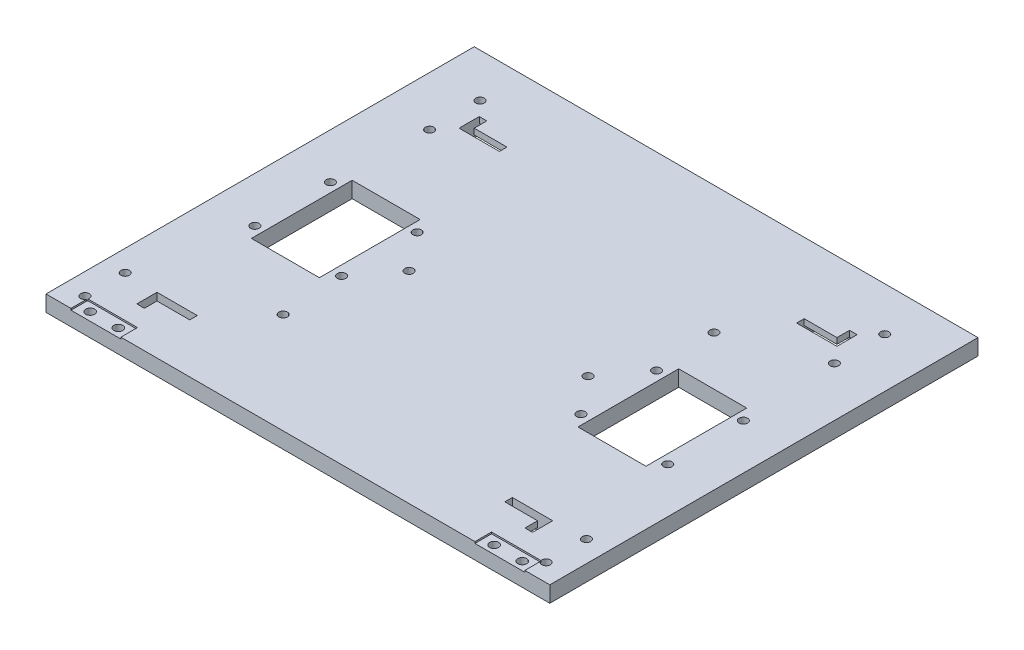
SolidWorks part; units mm, degrees
material "1023 Carbon Steel Sheet (SS)"
ref_plane "Front Plane" through (0, 0, 0) normal (0, 0, 1) x (1, 0, 0)
ref_plane "Top Plane" through (0, 0, 0) normal (0, 1, 0) x (1, 0, 0)
ref_plane "Right Plane" through (0, 0, 0) normal (1, 0, 0) x (0, 0, -1)
sketch "Sketch1" plane through (0, 0, 0) normal (0, 1, 0) x (1, 0, 0)
  line L1 (-100, -85) -> (100, -85)
  line L2 (-100, -85) -> (-100, 85)
  line L3 (-100, 85) -> (100, 85)
  line L4 (100, -85) -> (100, 85)
  line L5 (-100, -85) -> (100, 85) construction
  line L6 (-100, 85) -> (100, -85) construction
  point P0 (0, 0)
  dimension "D1" = 200
  dimension "D2" = 170
extrude "1/4\" Steel Plate" add sketch "Sketch1" along normal blind 6.35
ref_plane "Midplane" through (0, 0, 0) normal (-1, 0, 0) x (0, 0, 1)
sketch "Sketch2" plane through (0, 6.35, 0) normal (0, 1, 0) x (1, 0, 0)
  line L0 (-100, -85) -> (100, -85) construction
  line L1 (-90.094, -85) -> (-70.282, -85)
  line L2 (-90.094, -85) -> (-90.094, -78.396)
  line L3 (-90.094, -78.396) -> (-70.282, -78.396)
  line L4 (-70.282, -85) -> (-70.282, -78.396)
  line L5 (-100, 85) -> (-100, -85) construction
  dimension "D1" = 9.906
  dimension "D2" = 6.604
  dimension "D3" = 19.812
extrude "BladeHingeCut" cut sketch "Sketch2" against normal blind 0.635
hole_wizard "BladeHingeHole" positions "3DSketch2" profile "Sketch4" hole size "#8" standard "ANSI Inch" end condition through all
sketch3d "3DSketch2"
  line L0 (-90.094, 5.715, 85) -> (-70.282, 5.715, 85) construction
  line L10 (-80.188, 5.715, 78.396) -> (-80.188, 5.715, 85) construction
  line L11 (-70.282, 5.715, 78.396) -> (-90.094, 5.715, 78.396) construction
  point P0 (-74.6, 5.715, 81.698)
  point P2 (-85.776, 5.715, 81.698)
  dimension "D1" = 3.302
  dimension "D2" = 3.302
  dimension "D3" = 11.176
  dimension "D4" = 5.588
sketch "Sketch4" plane through (-74.6, 5.715, 81.698) normal (1, 0, 0) x (0, 0, 1)
  line L0 (0, 0) -> (0, 5.715)
  line L1 (0, 5.715) -> (1.778, 5.715)
  line L2 (1.778, 5.715) -> (1.778, 0)
  line L5 (1.778, 0) -> (0, 0)
  line L11 (0, -6.35) -> (0, 107.95) construction
  dimension "Thru Hole Dia." = 3.556
  dimension "Thru Hole Depth" = 5.715
sketch "Sketch5" plane through (0, 0, 0) normal (0, -1, 0) x (1, 0, 0)
  line L1 (-88.301, 79.173) -> (-83.251, 79.173)
  line L2 (-88.301, 79.173) -> (-88.301, 84.223)
  line L3 (-88.301, 84.223) -> (-83.251, 84.223)
  line L4 (-83.251, 79.173) -> (-83.251, 84.223)
  line L5 (-88.301, 79.173) -> (-83.251, 84.223) construction
  line L6 (-88.301, 84.223) -> (-83.251, 79.173) construction
  line L7 (-72.075, 79.173) -> (-77.125, 79.173)
  line L8 (-72.075, 79.173) -> (-72.075, 84.223)
  line L9 (-72.075, 84.223) -> (-77.125, 84.223)
  line L10 (-77.125, 79.173) -> (-77.125, 84.223)
  line L11 (-72.075, 79.173) -> (-77.125, 84.223) construction
  line L12 (-72.075, 84.223) -> (-77.125, 79.173) construction
  point P0 (-85.776, 81.698)
  point P6 (-74.6, 81.698)
  dimension "D1" = 5.05
  dimension "D2" = 5.05
  dimension "D3" = 5.05
  dimension "D4" = 5.05
extrude "BladeNutCut" cut sketch "Sketch5" against normal blind 2
mirror "BladeHingeMirror" about plane through (0, 0, 0) normal (-1, 0, 0) of "BladeNutCut", "BladeHingeHole", "BladeHingeCut"
sketch "Sketch6" plane through (0, 0, 0) normal (0, -1, 0) x (-1, 0, 0)
  line L0 (77.3259, -27.0397) -> (77.3259, 16.7603) construction
  line L1 (78.3259, 14.8603) -> (51.3259, 14.8603)
  line L2 (78.3259, 14.8603) -> (78.3259, -25.1397)
  line L3 (78.3259, -25.1397) -> (51.3259, -25.1397)
  line L4 (51.3259, 14.8603) -> (51.3259, -25.1397)
  line L5 (57.3259, 16.7603) -> (57.3259, -27.0397) construction
  point P6 (78.3259, -5.1397)
  dimension "D1" = 1
  dimension "D2" = 20
  dimension "D3" = 6
  dimension "D4" = 20
extrude "Cut-Extrude1" cut sketch "Sketch6" against normal up to surface (6.35 mm away) up to face at (0, 6.35, 54.4653)
sketch "Sketch7" plane through (0, 0, 0) normal (0, -1, 0) x (-1, 0, 0)
  line L0 (51.3259, -25.1397) -> (78.3259, -25.1397) construction
  line L1 (79.3259, -30.1397) -> (49.3259, -30.1397)
  line L2 (79.3259, -30.1397) -> (79.3259, -40.1397)
  line L3 (79.3259, -40.1397) -> (49.3259, -40.1397)
  line L4 (49.3259, -30.1397) -> (49.3259, -40.1397)
  line L5 (80.3259, 19.8603) -> (50.3259, 19.8603)
  line L6 (80.3259, 19.8603) -> (80.3259, 29.8603)
  line L7 (80.3259, 29.8603) -> (50.3259, 29.8603)
  line L8 (50.3259, 19.8603) -> (50.3259, 29.8603)
  line L9 (29.3259, -25.1397) -> (19.3259, -25.1397)
  line L10 (29.3259, -25.1397) -> (29.3259, 14.8603)
  line L11 (29.3259, 14.8603) -> (19.3259, 14.8603)
  line L12 (19.3259, -25.1397) -> (19.3259, 14.8603)
  line L17 (78.3259, -25.1397) -> (78.3259, 14.8603) construction
  line L18 (78.3259, 14.8603) -> (51.3259, 14.8603) construction
  line L19 (51.3259, 14.8603) -> (51.3259, -25.1397) construction
  line L29 (46.3259, -80.1397) -> (36.3259, -80.1397)
  line L30 (46.3259, -80.1397) -> (46.3259, -50.1397)
  line L31 (46.3259, -50.1397) -> (36.3259, -50.1397)
  line L32 (36.3259, -80.1397) -> (36.3259, -50.1397)
  line L33 (20, -70.1397) -> (-20, -70.1397)
  line L34 (20, -70.1397) -> (20, -60.1397)
  line L35 (20, -60.1397) -> (-20, -60.1397)
  line L36 (-20, -70.1397) -> (-20, -60.1397)
  line L37 (-100, 85) -> (100, 85) construction
  line L38 (36.3259, 39.8603) -> (46.3259, 39.8603)
  line L39 (36.3259, 39.8603) -> (36.3259, 69.8603)
  line L40 (36.3259, 69.8603) -> (46.3259, 69.8603)
  line L41 (46.3259, 39.8603) -> (46.3259, 69.8603)
  line L42 (20, 49.8603) -> (-20, 49.8603)
  line L43 (20, 49.8603) -> (20, 59.8603)
  line L44 (20, 59.8603) -> (-20, 59.8603)
  line L45 (-20, 49.8603) -> (-20, 59.8603)
  point P18 (0, 49.8603)
  point P55 (20, 54.8603)
  point P56 (36.3259, 54.8603)
  point P57 (20, -65.1397)
  point P58 (36.3259, -65.1397)
  point P60 (0, 85)
  dimension "D1" = 5
  dimension "D2" = 30
  dimension "D3" = 10
  dimension "D4" = 1
  dimension "D5" = 5
  dimension "D6" = 1
  dimension "D7" = 10
  dimension "D8" = 30
  dimension "D9" = 40
  dimension "D10" = 10
  dimension "D11" = 22
  dimension "D14" = 10
  dimension "D17" = 5
  dimension "D18" = 40
  dimension "D19" = 10
  dimension "D20" = 30
  dimension "D21" = 25
  dimension "D22" = 10
  dimension "D23" = 30
  dimension "D24" = 25
  dimension "D25" = 10
  dimension "D26" = 40
other "AlignGroup1"
extrude "Cut-Extrude2" cut sketch "Sketch7" against normal blind 5 contours L30 L29 L32 L31 | L34 L33 L36 L35 | L10 L9 L12 L11 | L2 L1 L4 L3 | L6 L5 L8 L7 | L39 L38 L41 L40 | L43 L42 L45 L44
sketch "Sketch8" plane through (0, 6.35, 0) normal (0, 1, 0) x (1, 0, 0)
  line L0 (-83.5459, -55) -> (-83.5459, -85) construction
  line L1 (-78.5459, -62.396) -> (-62.5459, -62.396)
  line L2 (-78.5459, -62.396) -> (-78.5459, -73.396)
  line L3 (-78.5459, -73.396) -> (-62.5459, -73.396)
  line L4 (-62.5459, -62.396) -> (-62.5459, -73.396)
  line L5 (-70.282, -78.396) -> (-90.094, -78.396) construction
  dimension "D1" = 11
  dimension "D2" = 16
  dimension "D3" = 5
  dimension "D4" = 5
extrude "Cut-Extrude3" cut sketch "Sketch8" along normal blind 4 from surface starting at face at (0, 0, -54.8603)
sketch "Sketch9" plane through (0, 4, 0) normal (0, -1, 0) x (1, 0, 0)
  line L0 (-78.5459, 62.396) -> (-62.5459, 62.396)
  line L9 (-78.5459, 62.396) -> (-78.5459, 70.396)
  line L10 (-78.5459, 73.396) -> (-78.5459, 62.396) construction
  line L11 (-78.5459, 70.396) -> (-75.5459, 70.396)
  line L12 (-75.5459, 70.396) -> (-75.5459, 65.396)
  line L13 (-75.5459, 65.396) -> (-62.5459, 65.396)
  line L14 (-62.5459, 62.396) -> (-62.5459, 73.396) construction
  line L15 (-62.5459, 65.396) -> (-62.5459, 62.396)
  dimension "D1" = 8
  dimension "D2" = 3
  dimension "D3" = 3
extrude "Cut-Extrude4" cut sketch "Sketch9" against normal up to surface (2.35 mm away) contours L13 L15 L0 L9 L11 L12 up to face at (-64.8259, 6.35, 5.1397)
sketch "Sketch10" plane through (0, 0, 0) normal (0, -1, 0) x (-1, 0, 0)
  line L1 (75, 65) -> (59, 65)
  line L2 (75, 65) -> (75, 54)
  line L3 (75, 54) -> (59, 54)
  line L4 (59, 65) -> (59, 54)
  line L6 (100, 85) -> (100, -85) construction
  line L7 (-100, 85) -> (100, 85) construction
  dimension "D1" = 11
  dimension "D2" = 16
  dimension "D3" = 25
  dimension "D4" = 20
extrude "Cut-Extrude5" cut sketch "Sketch10" against normal blind 4
sketch "Sketch11" plane through (0, 4, 0) normal (0, -1, 0) x (1, 0, 0)
  line L0 (-59, -54) -> (-75, -54)
  line L1 (-75, -54) -> (-75, -62)
  line L2 (-75, -54) -> (-75, -65) construction
  line L3 (-75, -62) -> (-72, -62)
  line L4 (-72, -62) -> (-72, -57)
  line L5 (-72, -57) -> (-59, -57)
  line L6 (-59, -65) -> (-59, -54) construction
  line L7 (-59, -57) -> (-59, -54)
  dimension "D1" = 3
  dimension "D2" = 3
  dimension "D3" = 8
extrude "Cut-Extrude6" cut sketch "Sketch11" against normal up to next
mirror "Mirror2" about plane through (0, 0, 0) normal (-1, 0, 0) of "Cut-Extrude6", "Cut-Extrude5", "Cut-Extrude4", "Cut-Extrude3", "Cut-Extrude2", "Cut-Extrude1"
hole_wizard "CSK for M3 Flat Head Machine Screw1" positions "Sketch12" profile "Sketch13" countersink size "M3" standard "ANSI Metric"
sketch "Sketch12" plane through (0, 0, 0) normal (0, -1, 0) x (-1, 0, 0)
  point P0 (-91.5503, -78)
  point P2 (-91.5503, -62)
  point P4 (-80.3371, 47.6378)
  point P7 (-80.3371, 67.6378)
  point P10 (-35.8509, -5.663)
  point P13 (-45.8509, 34.337)
  point P16 (35.8509, -5)
  point P19 (45.8509, -45)
  point P22 (91.5459, -62)
  point P25 (91.5459, -78)
  point P28 (80.3371, 47.6378)
  point P31 (80.3371, 67.6378)
  point P39 (-81.9659, -20.1397)
  point P42 (-81.9659, 9.8603)
  point P45 (-47.5109, -20.1397)
  point P48 (-47.5109, 9.8603)
  point P51 (47.5109, -20.1397)
  point P54 (81.9659, -20.1397)
  point P57 (81.9659, 9.8603)
  point P60 (47.5109, 9.8603)
  point P63 (-50.2355, -20.5233)
  point P64 (0, 0)
  point P65 (-52.2355, -20.5233)
sketch "Sketch13" plane through (91.5503, 0, 78) normal (1, 0, 0) x (0, 0, -1)
  line L0 (0, 0) -> (0, 14)
  line L1 (0, 14) -> (1.7, 14)
  line L2 (1.7, 14) -> (1.7, 1.45)
  line L3 (1.7, 1.45) -> (3.15, 0)
  line L5 (3.15, 0) -> (0, 0)
  line L6 (-1.7, 1.45) -> (-3.15, 0) construction
  line L10 (0, 14) -> (-1.7, 14) construction
  line L11 (0, -6.35) -> (0, 107.95) construction
  dimension "Hole Dia." = 3.4
  dimension "Hole Depth" = 14
  dimension "Near C'Sink Dia." = 6.3
  dimension "Near C'Sink Angle" = 90
  dimension "Drill Angle" = 180
